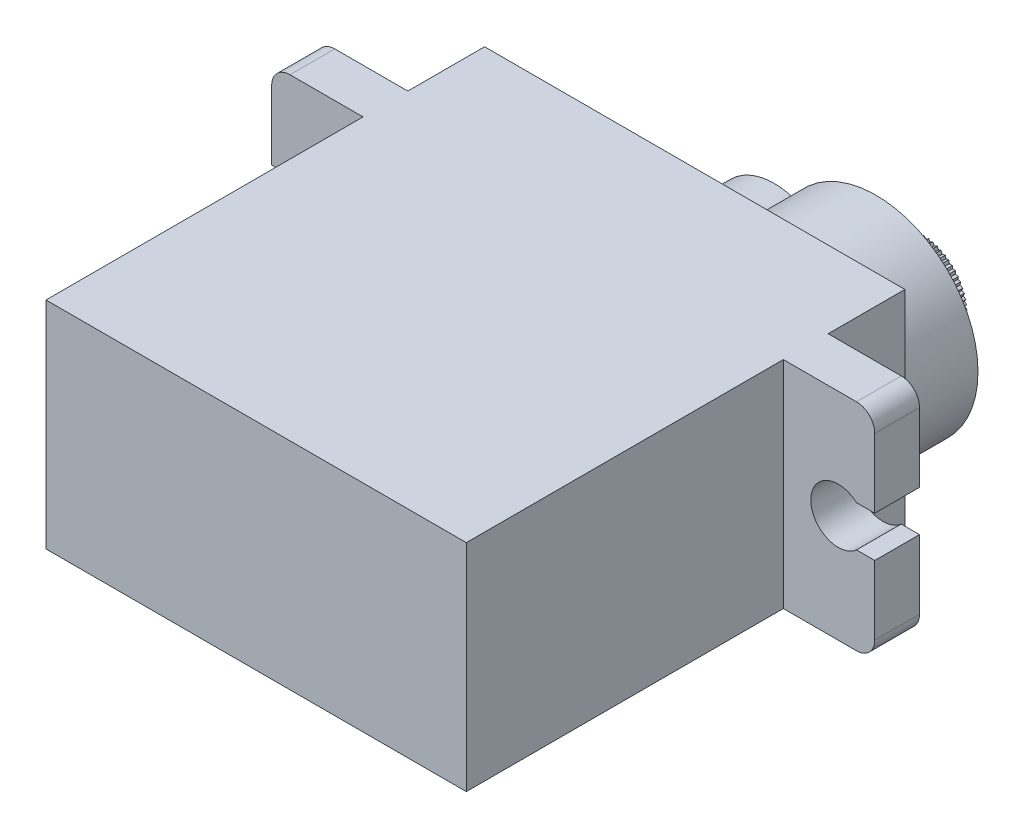
SolidWorks part; units mm, degrees
ref_plane "Ön Düzlem" through (0, 0, 0) normal (0, 0, 1) x (1, 0, 0)
ref_plane "Üst Düzlem" through (0, 0, 0) normal (0, 1, 0) x (1, 0, 0)
ref_plane "Sağ Düzlem" through (0, 0, 0) normal (1, 0, 0) x (0, 0, -1)
sketch "Çizim1" plane through (0, 0, 0) normal (0, 0, 1) x (1, 0, 0)
  line L1 (-11.5, -5.9) -> (11.5, -5.9)
  line L2 (-11.5, -5.9) -> (-11.5, 5.9)
  line L3 (-11.5, 5.9) -> (11.5, 5.9)
  line L4 (11.5, -5.9) -> (11.5, 5.9)
  line L5 (-11.5, -5.9) -> (11.5, 5.9) construction
  line L6 (-11.5, 5.9) -> (11.5, -5.9) construction
  point P0 (0, 0)
  dimension "D1" = 23
  dimension "D2" = 11.8
extrude "Yükseklik-Ekstrüzyon1" add sketch "Çizim1" along normal blind 17.35
sketch "Çizim4" plane through (11.5, 0, 0) normal (1, 0, 0) x (0, 0, -1)
  line L0 (-17.35, -5.9) -> (0, -5.9) construction
  line L1 (0, 5.9) -> (2.45, 5.9)
  line L2 (0, 5.9) -> (0, -5.9)
  line L3 (0, -5.9) -> (2.45, -5.9)
  line L4 (2.45, 5.9) -> (2.45, -5.9)
  dimension "D1" = 2.45
extrude "Yükseklik-Ekstrüzyon2" add sketch "Çizim4" along normal blind 5
sketch "Çizim5" plane through (-11.5, 0, 0) normal (-1, 0, 0) x (0, 0, 1)
  line L0 (17.35, 5.9) -> (0, 5.9) construction
  line L1 (0, -5.9) -> (-2.45, -5.9)
  line L2 (0, -5.9) -> (0, 5.9)
  line L3 (0, 5.9) -> (-2.45, 5.9)
  line L4 (-2.45, -5.9) -> (-2.45, 5.9)
  dimension "D1" = 2.45
extrude "Yükseklik-Ekstrüzyon3" add sketch "Çizim5" along normal blind 5
sketch "Çizim6" plane through (16.5, 0, 0) normal (1, 0, 0) x (0, 0, -1)
  line L0 (0, 0) -> (2.45, 0) construction
  line L1 (0, 5.9) -> (0, -5.9) construction
  line L2 (2.45, -5.9) -> (2.45, 5.9) construction
  line L4 (2.45, 1.12) -> (0, 1.12)
  line L5 (2.45, 1.12) -> (2.45, -1.12)
  line L6 (2.45, -1.12) -> (0, -1.12)
  line L7 (0, 1.12) -> (0, -1.12)
  line L8 (2.45, 1.12) -> (0, -1.12) construction
  line L9 (2.45, -1.12) -> (0, 1.12) construction
  point P6 (1.225, 0)
  dimension "D1" = 2.24
sketch "Çizim7" plane through (0, 0, 0) normal (0, 0, -1) x (-1, 0, 0)
  line L0 (-11.5, 5.9) -> (11.5, 5.9) construction
  line L1 (-11.5, -5.9) -> (11.5, -5.9)
  line L2 (-11.5, -5.9) -> (-11.5, 5.9)
  line L3 (-11.5, 5.9) -> (11.5, 5.9)
  line L4 (11.5, -5.9) -> (11.5, 5.9)
  line L5 (-11.5, -5.9) -> (11.5, 5.9) construction
  line L6 (-11.5, 5.9) -> (11.5, -5.9) construction
  point P0 (0, 0)
  dimension "D1" = 23
extrude "Yükseklik-Ekstrüzyon4" add sketch "Çizim7" along normal blind 6.65
sketch "Çizim8" plane through (0, 0, -2.45) normal (0, 0, -1) x (-1, 0, 0)
  line L0 (0, 0.2404) -> (0, 3.5063) construction
  circle A0 centre (-14.5, 0) radius 1.5
  circle A1 centre (14.5, 0) radius 1.5
  dimension "D2" = 3
  dimension "D1" = 3
extrude "Kes-Ekstrüzyon1" cut sketch "Çizim8" against normal up to surface (2.45 mm away) up to face at (14, 0, 0)
fillet "Radyus1" radius 1 4 edges at (-16.5, 5.9, -1.225) (-16.5, -5.9, -1.225) (16.5, -5.9, -1.225) (16.5, 5.9, -1.225)
extrude "Kes-Ekstrüzyon2" cut sketch "Çizim6" against normal blind 1
sketch "Çizim9" plane through (-16.5, 0, 0) normal (-1, 0, 0) x (0, 0, 1)
  line L0 (0, 0) -> (-2.45, 0) construction
  line L1 (-2.45, 5.9) -> (-2.45, -5.9) construction
  line L2 (0, -5.9) -> (0, 5.9) construction
  line L3 (-2.45, -1.12) -> (0, -1.12)
  line L4 (-2.45, -1.12) -> (-2.45, 1.12)
  line L5 (-2.45, 1.12) -> (0, 1.12)
  line L6 (0, -1.12) -> (0, 1.12)
  line L7 (-2.45, -1.12) -> (0, 1.12) construction
  line L8 (-2.45, 1.12) -> (0, -1.12) construction
  point P5 (-1.225, 0)
  dimension "D1" = 2.24
extrude "Kes-Ekstrüzyon3" cut sketch "Çizim9" against normal blind 1
sketch "Çizim10" plane through (0, 0, -6.65) normal (0, 0, -1) x (-1, 0, 0)
  line L0 (-11.5, 0) -> (-5.925, 0) construction
  line L1 (-11.5, 5.9) -> (-11.5, -5.9) construction
  circle A0 centre (-5.925, 0) radius 5.575
  dimension "D2" = 11.15
  dimension "D1" = 5.575
extrude "Yükseklik-Ekstrüzyon5" add sketch "Çizim10" along normal blind 4
sketch "Çizim11" plane through (0, 0, -10.65) normal (0, 0, -1) x (-1, 0, 0)
  circle A0 centre (-5.925, 0) radius 2.5
  dimension "D1" = 5
extrude "Yükseklik-Ekstrüzyon6" add sketch "Çizim11" along normal blind 2.5
sketch "Çizim12" plane through (0, 0, -6.65) normal (0, 0, -1) x (-1, 0, 0)
  line L0 (-0.35, 0) -> (3, 0) construction
  circle A0 centre (-5.925, 0) radius 5.575 construction
  circle A1 centre (-5.925, 0) radius 5.575 construction
  circle A2 centre (-0.35, 0) radius 3.35
  dimension "D1" = 3.35
extrude "Yükseklik-Ekstrüzyon7" add sketch "Çizim12" along normal blind 4
sketch "Çizim13" plane through (0, 0, -13.15) normal (0, 0, -1) x (-1, 0, 0)
  line L0 (-5.925, 2.375) -> (-5.815, 2.485)
  line L1 (-5.925, 2.375) -> (-6.035, 2.485)
  line L2 (-6.035, 2.485) -> (-6.1562, 2.3637)
  line L3 (-5.815, 2.485) -> (-5.6938, 2.3637)
  line L4 (-5.5481, 2.4587) -> (-5.6906, 2.3634)
  line L5 (-5.4617, 2.3294) -> (-5.5481, 2.4587)
  line L6 (-5.4617, 2.3294) -> (-5.3324, 2.4158)
  line L7 (-5.3324, 2.4158) -> (-5.2371, 2.2732)
  line L8 (-5.0756, 2.3379) -> (-5.234, 2.2723)
  line L9 (-5.0161, 2.1942) -> (-5.0756, 2.3379)
  line L10 (-5.0161, 2.1942) -> (-4.8725, 2.2537)
  line L11 (-4.8725, 2.2537) -> (-4.8068, 2.0953)
  line L12 (-4.6359, 2.1273) -> (-4.804, 2.0938)
  line L13 (-4.6055, 1.9747) -> (-4.6359, 2.1273)
  line L14 (-4.6055, 1.9747) -> (-4.453, 2.0051)
  line L15 (-4.453, 2.0051) -> (-4.4196, 1.8369)
  line L16 (-4.2456, 1.8349) -> (-4.4171, 1.8349)
  line L17 (-4.2456, 1.6794) -> (-4.2456, 1.8349)
  line L18 (-4.2456, 1.6794) -> (-4.0901, 1.6794)
  line L19 (-4.0901, 1.6794) -> (-4.0901, 1.5079)
  line L20 (-3.9199, 1.472) -> (-4.0881, 1.5054)
  line L21 (-3.9503, 1.3195) -> (-3.9199, 1.472)
  line L22 (-3.9503, 1.3195) -> (-3.7977, 1.2891)
  line L23 (-3.7977, 1.2891) -> (-3.8312, 1.121)
  line L24 (-3.6713, 1.0525) -> (-3.8297, 1.1182)
  line L25 (-3.7308, 0.9089) -> (-3.6713, 1.0525)
  line L26 (-3.7308, 0.9089) -> (-3.5871, 0.8494)
  line L27 (-3.5871, 0.8494) -> (-3.6527, 0.691)
  line L28 (-3.5092, 0.5926) -> (-3.6518, 0.6879)
  line L29 (-3.5956, 0.4633) -> (-3.5092, 0.5926)
  line L30 (-3.5956, 0.4633) -> (-3.4663, 0.3769)
  line L31 (-3.4663, 0.3769) -> (-3.5616, 0.2344)
  line L32 (-3.44, 0.11) -> (-3.5613, 0.2312)
  line L33 (-3.55, 0) -> (-3.44, 0.11)
  line L34 (-3.55, 0) -> (-3.44, -0.11)
  line L35 (-3.44, -0.11) -> (-3.5613, -0.2312)
  line L36 (-3.4663, -0.3769) -> (-3.5616, -0.2344)
  line L37 (-3.5956, -0.4633) -> (-3.4663, -0.3769)
  line L38 (-3.5956, -0.4633) -> (-3.5092, -0.5926)
  line L39 (-3.5092, -0.5926) -> (-3.6518, -0.6879)
  line L40 (-3.5871, -0.8494) -> (-3.6527, -0.691)
  line L41 (-3.7308, -0.9089) -> (-3.5871, -0.8494)
  line L42 (-3.7308, -0.9089) -> (-3.6713, -1.0525)
  line L43 (-3.6713, -1.0525) -> (-3.8297, -1.1182)
  line L44 (-3.7977, -1.2891) -> (-3.8312, -1.121)
  line L45 (-3.9503, -1.3195) -> (-3.7977, -1.2891)
  line L46 (-3.9503, -1.3195) -> (-3.9199, -1.472)
  line L47 (-3.9199, -1.472) -> (-4.0881, -1.5054)
  line L48 (-4.0901, -1.6794) -> (-4.0901, -1.5079)
  line L49 (-4.2456, -1.6794) -> (-4.0901, -1.6794)
  line L50 (-4.2456, -1.6794) -> (-4.2456, -1.8349)
  line L51 (-4.2456, -1.8349) -> (-4.4171, -1.8349)
  line L52 (-4.453, -2.0051) -> (-4.4196, -1.8369)
  line L53 (-4.6055, -1.9747) -> (-4.453, -2.0051)
  line L54 (-4.6055, -1.9747) -> (-4.6359, -2.1273)
  line L55 (-4.6359, -2.1273) -> (-4.804, -2.0938)
  line L56 (-4.8725, -2.2537) -> (-4.8068, -2.0953)
  line L57 (-5.0161, -2.1942) -> (-4.8725, -2.2537)
  line L58 (-5.0161, -2.1942) -> (-5.0756, -2.3379)
  line L59 (-5.0756, -2.3379) -> (-5.234, -2.2723)
  line L60 (-5.3324, -2.4158) -> (-5.2371, -2.2732)
  line L61 (-5.4617, -2.3294) -> (-5.3324, -2.4158)
  line L62 (-5.4617, -2.3294) -> (-5.5481, -2.4587)
  line L63 (-5.5481, -2.4587) -> (-5.6906, -2.3634)
  line L64 (-5.815, -2.485) -> (-5.6938, -2.3637)
  line L65 (-5.925, -2.375) -> (-5.815, -2.485)
  line L66 (-5.925, -2.375) -> (-6.035, -2.485)
  line L67 (-6.035, -2.485) -> (-6.1562, -2.3637)
  line L68 (-6.3019, -2.4587) -> (-6.1594, -2.3634)
  line L69 (-6.3883, -2.3294) -> (-6.3019, -2.4587)
  line L70 (-6.3883, -2.3294) -> (-6.5176, -2.4158)
  line L71 (-6.5176, -2.4158) -> (-6.6129, -2.2732)
  line L72 (-6.7744, -2.3379) -> (-6.616, -2.2723)
  line L73 (-6.8339, -2.1942) -> (-6.7744, -2.3379)
  line L74 (-6.8339, -2.1942) -> (-6.9775, -2.2537)
  line L75 (-6.9775, -2.2537) -> (-7.0432, -2.0953)
  line L76 (-7.2141, -2.1273) -> (-7.046, -2.0938)
  line L77 (-7.2445, -1.9747) -> (-7.2141, -2.1273)
  line L78 (-7.2445, -1.9747) -> (-7.397, -2.0051)
  line L79 (-7.397, -2.0051) -> (-7.4304, -1.8369)
  line L80 (-7.6044, -1.8349) -> (-7.4329, -1.8349)
  line L81 (-7.6044, -1.6794) -> (-7.6044, -1.8349)
  line L82 (-7.6044, -1.6794) -> (-7.7599, -1.6794)
  line L83 (-7.7599, -1.6794) -> (-7.7599, -1.5079)
  line L84 (-7.9301, -1.472) -> (-7.7619, -1.5054)
  line L85 (-7.8997, -1.3195) -> (-7.9301, -1.472)
  line L86 (-7.8997, -1.3195) -> (-8.0523, -1.2891)
  line L87 (-8.0523, -1.2891) -> (-8.0188, -1.121)
  line L88 (-8.1787, -1.0525) -> (-8.0203, -1.1182)
  line L89 (-8.1192, -0.9089) -> (-8.1787, -1.0525)
  line L90 (-8.1192, -0.9089) -> (-8.2629, -0.8494)
  line L91 (-8.2629, -0.8494) -> (-8.1973, -0.691)
  line L92 (-8.3408, -0.5926) -> (-8.1982, -0.6879)
  line L93 (-8.2544, -0.4633) -> (-8.3408, -0.5926)
  line L94 (-8.2544, -0.4633) -> (-8.3837, -0.3769)
  line L95 (-8.3837, -0.3769) -> (-8.2884, -0.2344)
  line L96 (-8.41, -0.11) -> (-8.2887, -0.2312)
  line L97 (-8.3, 0) -> (-8.41, -0.11)
  line L98 (-8.3, 0) -> (-8.41, 0.11)
  line L99 (-8.41, 0.11) -> (-8.2887, 0.2312)
  line L100 (-8.3837, 0.3769) -> (-8.2884, 0.2344)
  line L101 (-8.2544, 0.4633) -> (-8.3837, 0.3769)
  line L102 (-8.2544, 0.4633) -> (-8.3408, 0.5926)
  line L103 (-8.3408, 0.5926) -> (-8.1982, 0.6879)
  line L104 (-8.2629, 0.8494) -> (-8.1973, 0.691)
  line L105 (-8.1192, 0.9089) -> (-8.2629, 0.8494)
  line L106 (-8.1192, 0.9089) -> (-8.1787, 1.0525)
  line L107 (-8.1787, 1.0525) -> (-8.0203, 1.1182)
  line L108 (-8.0523, 1.2891) -> (-8.0188, 1.121)
  line L109 (-7.8997, 1.3195) -> (-8.0523, 1.2891)
  line L110 (-7.8997, 1.3195) -> (-7.9301, 1.472)
  line L111 (-7.9301, 1.472) -> (-7.7619, 1.5054)
  line L112 (-7.7599, 1.6794) -> (-7.7599, 1.5079)
  line L113 (-7.6044, 1.6794) -> (-7.7599, 1.6794)
  line L114 (-7.6044, 1.6794) -> (-7.6044, 1.8349)
  line L115 (-7.6044, 1.8349) -> (-7.4329, 1.8349)
  line L116 (-7.397, 2.0051) -> (-7.4304, 1.8369)
  line L117 (-7.2445, 1.9747) -> (-7.397, 2.0051)
  line L118 (-7.2445, 1.9747) -> (-7.2141, 2.1273)
  line L119 (-7.2141, 2.1273) -> (-7.046, 2.0938)
  line L120 (-6.9775, 2.2537) -> (-7.0432, 2.0953)
  line L121 (-6.8339, 2.1942) -> (-6.9775, 2.2537)
  line L122 (-6.8339, 2.1942) -> (-6.7744, 2.3379)
  line L123 (-6.7744, 2.3379) -> (-6.616, 2.2723)
  line L124 (-6.5176, 2.4158) -> (-6.6129, 2.2732)
  line L125 (-6.3883, 2.3294) -> (-6.5176, 2.4158)
  line L126 (-6.3883, 2.3294) -> (-6.3019, 2.4587)
  line L127 (-6.3019, 2.4587) -> (-6.1594, 2.3634)
  line L128 (-8.1973, 0.691) -> (-8.1982, 0.6879)
  line L129 (-8.0188, 1.121) -> (-8.0203, 1.1182)
  line L130 (-7.7599, 1.5079) -> (-7.7619, 1.5054)
  line L131 (-7.4304, 1.8369) -> (-7.4329, 1.8349)
  line L132 (-7.0432, 2.0953) -> (-7.046, 2.0938)
  line L133 (-6.6129, 2.2732) -> (-6.616, 2.2723)
  line L134 (-6.1562, 2.3637) -> (-6.1594, 2.3634)
  line L135 (-5.6906, 2.3634) -> (-5.6938, 2.3637)
  line L136 (-5.234, 2.2723) -> (-5.2371, 2.2732)
  line L137 (-4.804, 2.0938) -> (-4.8068, 2.0953)
  line L138 (-4.4171, 1.8349) -> (-4.4196, 1.8369)
  line L139 (-4.0881, 1.5054) -> (-4.0901, 1.5079)
  line L140 (-3.8297, 1.1182) -> (-3.8312, 1.121)
  line L141 (-3.6518, 0.6879) -> (-3.6527, 0.691)
  line L142 (-3.5613, 0.2312) -> (-3.5616, 0.2344)
  line L143 (-3.5616, -0.2344) -> (-3.5613, -0.2312)
  line L144 (-3.6527, -0.691) -> (-3.6518, -0.6879)
  line L145 (-3.8312, -1.121) -> (-3.8297, -1.1182)
  line L146 (-4.0901, -1.5079) -> (-4.0881, -1.5054)
  line L147 (-4.4196, -1.8369) -> (-4.4171, -1.8349)
  line L148 (-4.8068, -2.0953) -> (-4.804, -2.0938)
  line L149 (-5.2371, -2.2732) -> (-5.234, -2.2723)
  line L150 (-5.6938, -2.3637) -> (-5.6906, -2.3634)
  line L151 (-6.1594, -2.3634) -> (-6.1562, -2.3637)
  line L152 (-6.616, -2.2723) -> (-6.6129, -2.2732)
  line L153 (-7.046, -2.0938) -> (-7.0432, -2.0953)
  line L154 (-7.4329, -1.8349) -> (-7.4304, -1.8369)
  line L155 (-7.7619, -1.5054) -> (-7.7599, -1.5079)
  line L156 (-8.0203, -1.1182) -> (-8.0188, -1.121)
  line L157 (-8.1982, -0.6879) -> (-8.1973, -0.691)
  line L158 (-8.2887, -0.2312) -> (-8.2884, -0.2344)
  line L159 (-8.2884, 0.2344) -> (-8.2887, 0.2312)
  circle A1 centre (-5.925, 0) radius 2.5
  point P167 (-5.925, 0)
  point P229 (-5.925, 0)
  dimension "D1" = 32
  dimension "D2" = 32
extrude "Kes-Ekstrüzyon4" cut sketch "Çizim13" against normal up to surface (2.5 mm away) up to face at (3.425, 0, -10.65)
sketch "Çizim14" plane through (0, 0, -13.15) normal (0, 0, -1) x (-1, 0, 0)
  line L0 (-11.5, 0) -> (-5.925, 0) construction
  line L1 (-11.5, -5.9) -> (-11.5, 5.9) construction
  circle A0 centre (-5.925, 0) radius 0.75
  dimension "D1" = 1.5
extrude "Kes-Ekstrüzyon5" cut sketch "Çizim14" against normal blind 1
sketch "Çizim15" plane through (0, -5.9, 0) normal (0, -1, 0) x (1, 0, 0)
  line L0 (0, 17.35) -> (0, 15.35) construction
  line L1 (-11.5, 17.35) -> (11.5, 17.35) construction
  line L2 (-11.5, 8.675) -> (-9.5, 8.675) construction
  line L3 (-11.5, 17.35) -> (-11.5, 0) construction
  line L4 (11.5, 17.35) -> (11.5, 0) construction
  line L5 (-9.5, 15.35) -> (9.5, 15.35)
  line L6 (-9.5, 15.35) -> (-9.5, 2)
  line L7 (-9.5, 2) -> (9.5, 2)
  line L8 (9.5, 15.35) -> (9.5, 2)
  dimension "D1" = 2
  dimension "D2" = 2
  dimension "D3" = 2
  dimension "D4" = 2
  dimension "D5" = 2
extrude "Yükseklik-Ekstrüzyon8" add sketch "Çizim15" along normal blind 0.1
sketch "Çizim16" plane through (0, -6, 0) normal (0, -1, 0) x (1, 0, 0)
  line L0 (0, 2) -> (0, 5) construction
  line L1 (-9.5, 2) -> (9.5, 2) construction
  line L2 (9, 5) -> (-9, 5) construction
  text T0 "TOWER PRO" font "Century Gothic" height 2
  point P8 (0, 5)
extrude "Kes-Ekstrüzyon6" cut sketch "Çizim16" against normal blind 0.1
sketch "Çizim17" plane through (0, -6, 0) normal (0, -1, 0) x (1, 0, 0)
  line L0 (-9.5, 8.675) -> (9.5, 8.675) construction
  line L1 (-9.5, 15.35) -> (-9.5, 2) construction
  line L2 (9.5, 2) -> (9.5, 15.35) construction
  line L4 (-9.5, 6.925) -> (9.5, 6.925)
  line L5 (-9.5, 6.925) -> (-9.5, 10.425)
  line L6 (-9.5, 10.425) -> (9.5, 10.425)
  line L7 (9.5, 6.925) -> (9.5, 10.425)
  line L8 (-9.5, 6.925) -> (9.5, 10.425) construction
  line L9 (-9.5, 10.425) -> (9.5, 6.925) construction
  point P6 (0, 8.675)
  dimension "D1" = 3.5
extrude "Yükseklik-Ekstrüzyon9" add sketch "Çizim17" along normal blind 0.05
sketch "Çizim18" plane through (0, -6.05, 0) normal (0, -1, 0) x (1, 0, 0)
  line L0 (-9.5, 8.675) -> (9.5, 8.675) construction
  line L1 (-9.5, 10.425) -> (-9.5, 6.925) construction
  line L2 (9.5, 6.925) -> (9.5, 10.425) construction
  line L3 (9.5, 8.675) -> (9.5, 10.425) construction
  line L4 (9.5, 2) -> (9.5, 15.35) construction
  line L5 (9.5, 9.55) -> (-9.5, 9.55) construction
  text T0 "MİCRO SERVO" font "Century Gothic" height 1
  text T1 "90" font "Century Gothic" height 0.6
extrude "Kes-Ekstrüzyon7" cut sketch "Çizim18" against normal blind 0.05
sketch "Çizim19" plane through (0, -6, 0) normal (0, -1, 0) x (1, 0, 0)
  line L0 (9.5, 12.8875) -> (-9.5, 12.8875) construction
  line L1 (9.5, 10.425) -> (9.5, 15.35) construction
  line L2 (-9.5, 15.35) -> (-9.5, 10.425) construction
  text T0 "SG90" font "Century Gothic" height 1.5
extrude "Kes-Ekstrüzyon8" cut sketch "Çizim19" against normal blind 0.1
sketch "Çizim21" plane through (0, -5.9, 0) normal (0, -1, 0) x (1, 0, 0)
  line L11 (-9.5, 2) -> (9.5, 2) construction
  line L12 (9.5, 2) -> (9.5, 15.35) construction
  line L13 (-9.5, 15.35) -> (-9.5, 2) construction
  line L14 (9.5, 15.35) -> (-9.5, 15.35) construction
  line L15 (-9.75, 1.75) -> (9.75, 1.75)
  line L16 (9.75, 1.75) -> (9.75, 15.6)
  line L17 (-9.75, 15.6) -> (-9.75, 1.75)
  line L18 (9.75, 15.6) -> (-9.75, 15.6)
  line L19 (-9.75, 1.75) -> (9.75, 1.75)
  line L20 (9.75, 1.75) -> (9.75, 15.6)
  line L21 (-9.75, 15.6) -> (-9.75, 1.75)
  line L22 (9.75, 15.6) -> (-9.75, 15.6)
  line L23 (-9.5, 2) -> (9.5, 2)
  line L24 (9.5, 2) -> (9.5, 15.35)
  line L25 (-9.5, 15.35) -> (-9.5, 2)
  line L26 (9.5, 15.35) -> (-9.5, 15.35)
  dimension "D1" = 0.25
extrude "Yükseklik-Ekstrüzyon10" add sketch "Çizim21" along normal blind 0.11
sketch "Çizim22" plane through (0, -5.9, 0) normal (0, -1, 0) x (1, 0, 0)
  line L0 (-9.75, 1.75) -> (9.75, 1.75) construction
  line L1 (9.75, 1.75) -> (9.75, 15.6) construction
  line L2 (9.75, 15.6) -> (-9.75, 15.6) construction
  line L3 (-9.75, 15.6) -> (-9.75, 1.75) construction
  line L4 (-9.75, 1.75) -> (9.75, 1.75)
  line L5 (9.75, 1.75) -> (9.75, 15.6)
  line L6 (9.75, 15.6) -> (-9.75, 15.6)
  line L7 (-9.75, 15.6) -> (-9.75, 1.75)
  line L8 (10, 15.85) -> (-10, 15.85)
  line L9 (-10, 15.85) -> (-10, 1.5)
  line L10 (-10, 1.5) -> (10, 1.5)
  line L11 (10, 1.5) -> (10, 15.85)
  dimension "D1" = 0.25
extrude "Yükseklik-Ekstrüzyon11" add sketch "Çizim22" along normal blind 0.1
